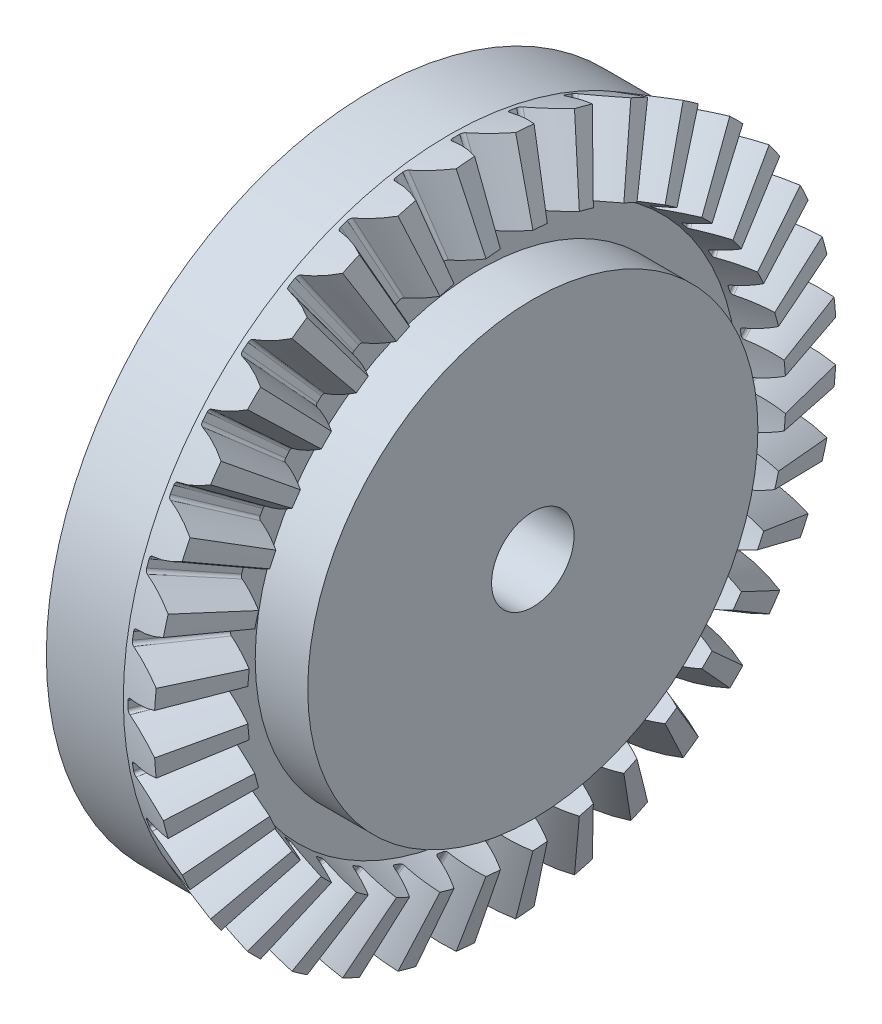
SolidWorks part; units mm, degrees
revolve "Base-Revolve" add sketch "BasProSke" angle 360 about L0 other way angle 5
sketch "BasProSke" plane through (0, 0, 0) normal (0, 1, 0) x (1, 0, 0)
  line L0 (-10, 0) -> (60, 0) construction
  line L1 (0, 0) -> (0, 8.684)
  line L2 (0, 0) -> (0.8323, 0)
  line L3 (0.8323, 0) -> (0.8323, 6.8532)
  line L4 (3.948, 0) -> (-9.0794, 39.0823) construction
  line L5 (0, 8.684) -> (1.2284, 9.0935)
  line L6 (3.948, 0) -> (-23.6442, 92.2592) construction
  line L7 (3.948, 0) -> (0, 8.684) construction
  line L8 (1.2284, 9.0935) -> (1.8018, 7.1764)
  line L9 (1.8018, 7.1764) -> (0.8323, 6.8532)
  line L10 (0.948, 9) -> (-11.0363, 9) construction
  dimension "D1" = 17.368
  dimension "D2" = 3.948
  dimension "D3" = 9.4868
  dimension "D4" = 1.784
ref_plane "Plane1" through (0, 0, 0) normal (0, 0, 1) x (1, 0, 0)
ref_plane "Plane2" through (0, 0, 0) normal (0, 1, 0) x (1, 0, 0)
ref_plane "Plane3" through (0, 0, 0) normal (1, 0, 0) x (0, 0, -1)
other "Configuration Table"
sketch "HoldingSke" plane through (0, 0, 0) normal (0, 1, 0) x (1, 0, 0)
  line L0 (0, 0) -> (1.618, -1.1756)
  line L1 (-15, 0) -> (100, 0) construction
  line L2 (0, 0) -> (-122.6628, 25.2748)
  line L3 (0, 0) -> (-11.863, 4.5341)
  line L4 (0, 0) -> (6.9867, 5.0761)
  line L5 (0, 0) -> (-5.6217, -2.0967)
  line L6 (0, 0) -> (-10.5278, -7.1032)
  line L7 (-122.6628, 25.2748) -> (-122.6177, 31.2747)
  line L8 (-76.2, 0.5) -> (-75.9, 0.5)
  line L9 (-71.009, 38.7566) -> (-53.1078, 45.2721)
  line L10 (-76.2, 71.12) -> (104.1128, 71.12)
  line L11 (0, 0) -> (-2, 0)
  line L12 (-76.2, 101.6) -> (-76.181, 101.6)
  line L13 (24.9733, 27.94) -> (52.9546, 28.2287)
  line L14 (24.9733, 27.94) -> (24.9743, 27.94)
  line L15 (24.9733, 27.94) -> (100.3893, 30.0425)
  line L16 (-122.6628, 25.2748) -> (3.6233, -1.5681)
  circle A0 centre (0, 0) radius 1
  circle A1 centre (0, 0) radius 8.684
  circle A2 centre (0, 0) radius 10
  circle A3 centre (0, 0) radius 1
  dimension "Num_teeth" = 36
  dimension "Pitch_radius" = 180.3128
  dimension "Width" = 2
ref_plane "ToothPln" through (0.6142, 8.8887, 0) normal (-0.3162, 0.9487, 0) x (0, 0, -1)
ref_plane "ToothPln2" through (0.3948, -1.1844, 0) normal (-0.3162, 0.9487, 0) x (0, 0, 1)
sketch "TooCutSke" plane through (0.6142, 8.8887, 0) normal (-0.3162, 0.9487, 0) x (0, 0, -1)
  line L2 (0, 8.6481) -> (144.0891, -1638.2981) construction
  line L3 (0, 8.6481) -> (78.8921, -1755.5054) construction
  line L4 (0, -15.621) -> (0, 105.791) construction
  line L6 (-24.765, -0.6474) -> (21.082, -0.6474) construction
  line L7 (0.7844, -0.3176) -> (0.4017, -0.3347) construction
  arc A0 (-0.6442, -0.8114) -> (0.6442, -0.8114) centre (0, 8.6481) ccw
  arc A1 (-0.094, 0.4481) -> (0.094, 0.4481) centre (0, 8.6481) ccw
  circle A2 centre (0, 8.6481) radius 9 construction
  circle A3 centre (0, 8.6481) radius 8.4572 construction
  arc A4 (0.1883, 0.3711) -> (0.094, 0.4481) centre (0.0951, 0.3531) ccw
  arc A5 (0.1883, 0.3711) -> (0.6442, -0.8114) centre (3.7229, 1.0544) ccw
  arc A6 (-0.6442, -0.8114) -> (-0.1883, 0.3711) centre (-3.7229, 1.0544) ccw
  arc A7 (-0.094, 0.4481) -> (-0.1883, 0.3711) centre (-0.0951, 0.3531) ccw
  ellipse E0 centre (0, 2.2282) end of major axis (9.0935, 2.2282) minor radius 2.8756 construction
sketch "TooCutSke2" plane through (0.3948, -1.1844, 0) normal (-0.3162, 0.9487, 0) x (0, 0, 1)
  line L0 (0, 0) -> (0, 68.072) construction
  line L2 (21.082, 2.7461) -> (-20.32, 2.7461) construction
  circle A0 centre (0, 3.7454) radius 0.0127
  ellipse E1 centre (0, 0) end of major axis (-8.684, 0) minor radius 2.7461 construction
loft "ToothCut" cut profiles "TooCutSke2", "TooCutSke"
pattern_circular "TeethCuts" count 36 every 10 about axis through (-10, 0, 0) along (1, 0, 0) of "ToothCut"
sketch "草图1" plane through (0.8323, 0, 0) normal (1, 0, 0) x (0, 0, -1)
  circle A0 centre (0, 0) radius 6
  dimension "D1" = 12
extrude "凸台-拉伸1" add sketch "草图1" along normal blind 1.4
sketch "HubSke" plane through (0, 0, 0) normal (-1, 0, 0) x (0, 0, 1)
  circle A0 centre (0, 0) radius 8.684
  dimension "Diameter" = 17.368
extrude "Hub" add sketch "HubSke" along normal blind 2.0521
sketch "BorSke" plane through (0, 0, 0) normal (1, 0, 0) x (0, 0, -1)
  circle A0 centre (0, 0) radius 1.1
  dimension "Diameter" = 2.2
extrude "Bore" cut sketch "BorSke" along normal mid plane 12.0001
sketch "KeySke" plane through (0, 0, 0) normal (1, 0, 0) x (0, 0, -1)
  line L0 (-0.4, 0) -> (-0.4, 1.3)
  line L1 (-0.4, 1.3) -> (0.4, 1.3)
  line L2 (0.4, 1.3) -> (0.4, 0)
  line L3 (0, 0) -> (0, 34) construction
  line L4 (-0.4, 0) -> (0.4, 0)
  dimension "Offset" = 1.3
extrude "Keyway" [suppressed] cut sketch "KeySke" along normal mid plane 12.0001
pattern_circular "Keyway2" [suppressed] count 2 every 90 about axis through (-10, 0, 0) along (1, 0, 0) reverse direction yes
equation "' \"Module@HoldingSke\" = 6.35"
equation "' \"Num_teeth@HoldingSke\" = 20"
equation "' \"Mating_teeth@HoldingSke\" = 12"
equation "' \"Ap@HoldingSke\" =  20"
equation "' \"Ap@HoldingSke\" = 20"
equation "' \"Width@HoldingSke\" = 0.5 * 25.4"
equation "' \"Hub_dia@HoldingSke\"= 2 * 25.4"
equation "' \"Hub_dia@HoldingSke\" = 2 * 25.4"
equation "' \"Mounting_dist@HoldingSke\" = 3 * 25.4"
equation "' \"Bore@HoldingSke\" = 19"
equation "' \"T_dim@HoldingSke\" = 0.1 * 25.4"
equation "' \"Width@KeySke\" = 0.25 * 25.4"
equation "' \"Show_teeth@HoldingSke\" = 100"
equation "' \"Backlash@HoldingSke\" = 0.009 * 25.4"
equation "' \"Addendum_fac@HoldingSke\" = 1.0"
equation "' \"Dedendum_fac@HoldingSke\" = 1.188"
equation "' \"Dedendum_add@HoldingSke\" = 0.002 * 25.4"
equation "' \"Clearance_fac@HoldingSke\" = 0.188"
equation "\"Pitch@HoldingSke\" = 1 / \"Module@HoldingSke\""
equation " \"Addendum_fac@HoldingSke\" = 0.54 + 0.46 / (\"Num_teeth@HoldingSke\" /  \"Mating_teeth@HoldingSke\" ) ^ 2"
equation "' \"Addendum_fac@HoldingSke\" = 2 - (0.54 + 0.46 / (\"Mating_teeth@HoldingSke\" /  \"Num_teeth@HoldingSke\" ) ^ 2)"
equation "\"Dedendum_fac@HoldingSke\" = 2.188 - \"Addendum_fac@HoldingSke\""
equation "\"Pitch_rad@BasProSke\" = \"Num_teeth@HoldingSke\" / \"Pitch@HoldingSke\" / 2"
equation "\"Pitch_ang@BasProSke\" = atn(\"Num_teeth@HoldingSke\" / \"Mating_teeth@HoldingSke\") * (180 / 3.14159265)"
equation "\"Addendum@BasProSke\" = \"Addendum_fac@HoldingSke\" / \"Pitch@HoldingSke\""
equation "\"Dedendum_plus@BasProSke\" = (\"Dedendum_fac@HoldingSke\" / \"Pitch@HoldingSke\" + \"Dedendum_add@HoldingSke\") * 1.25"
equation "\"Face_wid@BasProSke\" = \"Width@HoldingSke\""
equation "\"Radius@TooCutSke\" = ((\"Num_teeth@HoldingSke\" + 2 * \"Addendum_fac@HoldingSke\") / \"Pitch@HoldingSke\" ) / 2"
equation "\"Overcut_dia@TooCutSke\" =  1.02 * (\"Num_teeth@HoldingSke\" + 2 * \"Addendum_fac@HoldingSke\") / \"Pitch@HoldingSke\""
equation "\"Pitch_dia@TooCutSke\" = \"Num_teeth@HoldingSke\" / \"Pitch@HoldingSke\""
equation "\"Base_dia@TooCutSke\" = \"Num_teeth@HoldingSke\" / \"Pitch@HoldingSke\" * cos((\"Ap@HoldingSke\"  * 3.14159265 / 180))"
equation "'  \"Root_dia@TooCutSke\" =  (\"Num_teeth@HoldingSke\" + 2) / \"Pitch@HoldingSke\" - 2 * (\"Addendum_fac@HoldingSke\" + \"Dedendum_fac@HoldingSke\") / \"Pitch@HoldingSke\" - \"Dedendum_add@HoldingSke\" * 2"
equation "'  \"Root_dia@TooCutSke\" = (\"Num_teeth@HoldingSke\" + 2) / \"Pitch@HoldingSke\" - 2 * (\"Addendum_fac@HoldingSke\" + \"Dedendum_fac@HoldingSke\") / \"Pitch@HoldingSke\" - \"Dedendum_add@HoldingSke\" * 2"
equation "\"Root_dia@TooCutSke\" =  \"Num_teeth@HoldingSke\" / \"Pitch@HoldingSke\" -  2 * \"Dedendum_fac@HoldingSke\" / \"Pitch@HoldingSke\" - \"Dedendum_add@HoldingSke\" * 2"
equation "\"Half_ang@TooCutSke\" = 180 / \"Num_teeth@HoldingSke\""
equation "\"Half_CT@TooCutSke\" = \"Num_teeth@HoldingSke\" / \"Pitch@HoldingSke\" * sin((3.14159265 / 2 / \"Num_teeth@HoldingSke\")) / 2 - 2 * \"Backlash@HoldingSke\" / 4"
equation "\"Flank_rad@TooCutSke\" = \"Num_teeth@HoldingSke\" / \"Pitch@HoldingSke\" / 5"
equation "\"Root_fillet@TooCutSke\" = \"Clearance_fac@HoldingSke\" / \"Pitch@HoldingSke\" + \"Dedendum_add@HoldingSke\""
equation "\"Offset@ToothPln2\"  = \"Num_teeth@HoldingSke\" / \"Pitch@HoldingSke\" / 2 / sin(atn(\"Num_teeth@HoldingSke\" / \"Mating_teeth@HoldingSke\"))"
equation "\"Dedendum_plus@TooCutSke2\" = \"Dedendum_plus@BasProSke\""
equation "\"MHD@HoldingSke\" = \"Num_teeth@HoldingSke\" / \"Pitch@HoldingSke\" - 2 * \"Dedendum_plus@BasProSke\" * cos(atn(\"Num_teeth@HoldingSke\" / \"Mating_teeth@HoldingSke\"))"
equation "\"MBD@HoldingSke\" = \"Num_teeth@HoldingSke\" / \"Pitch@HoldingSke\" - 2 * \"Dedendum_plus@BasProSke\" * cos(atn(\"Num_teeth@HoldingSke\" / \"Mating_teeth@HoldingSke\")) - 0.002 * 25.4"
equation "\"MnMD@HoldingSke\" =  \"Num_teeth@HoldingSke\" / \"Pitch@HoldingSke\" / 2 / (\"Num_teeth@HoldingSke\" / \"Mating_teeth@HoldingSke\") + \"Dedendum_plus@BasProSke\" * sin(atn(\"Num_teeth@HoldingSke\" / \"Mating_teeth@HoldingSke\"))"
equation "\"OAL@HoldingSke\" = \"MnMD@HoldingSke\""
equation "\"MHD@HoldingSke\" = ((sgn( \"MHD@HoldingSke\" - \"Hub_dia@HoldingSke\" )-1)*( \"MHD@HoldingSke\" - \"Hub_dia@HoldingSke\" ))/-2+ \"Hub_dia@HoldingSke\""
equation "\"MBD@HoldingSke\" = ((sgn( \"MBD@HoldingSke\" - \"Bore@HoldingSke\" )-1)*( \"MBD@HoldingSke\" - \"Bore@HoldingSke\" ))/-2+ \"Bore@HoldingSke\""
equation "\"Face_wid@BasProSke\" = ((sgn( \"Face_wid@BasProSke\" - \"Offset@ToothPln2\" * 0.9)-1)*( \"Face_wid@BasProSke\" - \"Offset@ToothPln2\" * 0.9))/-2+ \"Offset@ToothPln2\" * 0.9"
equation "\"OAL@HoldingSke\" = ((sgn( \"OAL@HoldingSke\" - \"Mounting_dist@HoldingSke\" )+1)*( \"OAL@HoldingSke\" - \"Mounting_dist@HoldingSke\" ))/2 + \"Mounting_dist@HoldingSke\" + 0.000002 * 25.4"
equation "\"Num_teeth@TeethCuts\" = int( \"Show_teeth@HoldingSke\" ) + 1"
equation "\"Num_teeth@TeethCuts\" = ((sgn( \"Num_teeth@TeethCuts\" - \"Num_teeth@HoldingSke\" )-1)*( \"Num_teeth@TeethCuts\" - \"Num_teeth@HoldingSke\" ))/-2+ \"Num_teeth@HoldingSke\""
equation "\"Num_teeth@TeethCuts\" = ((sgn( \"Num_teeth@TeethCuts\" - 2.0)+1)*( \"Num_teeth@TeethCuts\" - 2.0))/2 +2.0"
equation "\"Angle@TeethCuts\" = 360.0 / \"Num_teeth@HoldingSke\""
equation "\"Diameter@HubSke\" = \"MHD@HoldingSke\""
equation "\"Length@Hub\" = \"OAL@HoldingSke\" - \"MnMD@HoldingSke\" + 0.000002 * 25.4"
equation "\"D1@Bore\" = \"OAL@HoldingSke\" * 2.0"
equation "\"D1@Keyway\" = \"OAL@HoldingSke\" * 2.0"
equation "\"Offset@KeySke\" = \"T_dim@HoldingSke\" + \"MBD@HoldingSke\" / 2.0"
